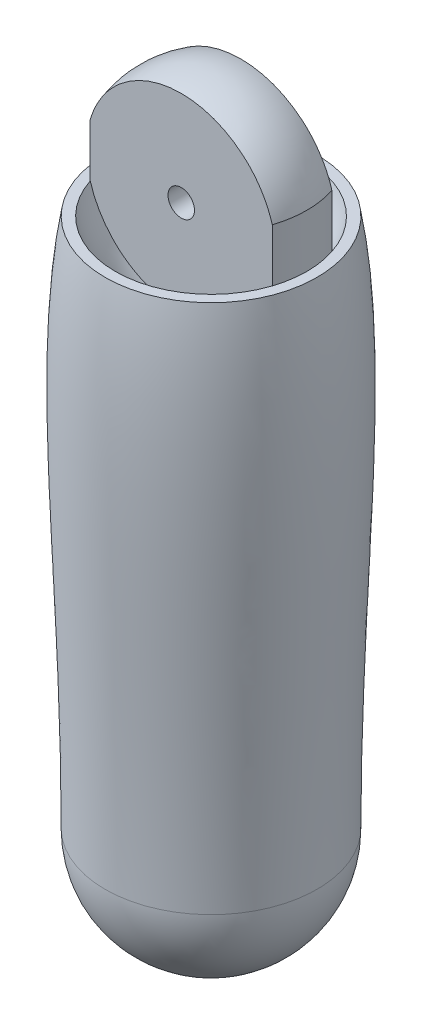
SolidWorks part; units mm, degrees
ref_plane "Front Plane" through (0, 0, 0) normal (0, 0, 1) x (1, 0, 0)
ref_plane "Top Plane" through (0, 0, 0) normal (0, 1, 0) x (1, 0, 0)
ref_plane "Right Plane" through (0, 0, 0) normal (1, 0, 0) x (0, 0, -1)
sketch "Sketch1" plane through (0, 0, 0) normal (1, 0, 0) x (0, 0, -1)
  line L0 (0, 20) -> (0, -20)
  line L1 (0, 20) -> (8, 20)
  line L2 (0, -20) -> (8, -20) construction
  line L3 (13.2094, -9.5442) -> (2.7906, 49.5442) construction
  line L4 (0, -20) -> (0, -28)
  arc A1 (8, -20) -> (0, -28) centre (0, -20) cw
  spline S0 degree 3 poles (8, 20) (9.7365, 10.1519) (8, -3.092) (8, -20) knots 0 0 0 0 1 1 1 1
  point P3 (0, 0)
  dimension "D3" = 100
  dimension "D4" = 30
  dimension "D1" = 40
  dimension "D2" = 8
revolve "Revolve1" add sketch "Sketch1" angle 360 about L0 region at (0, -2.8176, -4.1039)
sketch "Sketch4" plane through (0, 0, 0) normal (1, 0, 0) x (0, 0, -1)
  line L0 (0, 29.5) -> (0, 14.5)
  line L7 (8, 20) -> (-8, 20) construction
  arc A0 (0, 29.5) -> (0, 14.5) centre (0, 22) cw
  dimension "D1" = 15
  dimension "D2" = 2
revolve "Cut-Revolve1" cut sketch "Sketch4" angle 360 about L0
sketch "Sketch5" plane through (0, 0, 0) normal (0, 0, 1) x (1, 0, 0)
  line L1 (0, 14.5) -> (0, 29.5) construction
  line L2 (0, -55) -> (0, 55) construction
  circle A0 centre (0, 22) radius 7.5
extrude "Boss-Extrude1" add sketch "Sketch5" along normal mid plane 4.5
sketch "Sketch6" plane through (0, 20, 0) normal (0, 1, 0) x (1, 0, 0)
  arc A1 (6.8693, 2.25) -> (-6.8693, 2.25) centre (0, 0) ccw construction
  circle A2 centre (0, 0) radius 7.2284
extrude "Cut-Extrude3" cut sketch "Sketch6" along normal through all flip side to cut
ref_plane "Plane1" through (0, 22, 0) normal (0, 1, 0) x (1, 0, 0)
sketch "Sketch7" plane through (0, 22, 0) normal (0, 1, 0) x (1, 0, 0)
  line L0 (-10.1493, 0) -> (11.821, 0) construction
  line L4 (-7.5, 0) -> (-8.9317, 0)
  line L5 (-8.9317, 0) -> (-8.9317, 11.2726)
  line L6 (-8.9317, 11.2726) -> (9.3765, 11.2726)
  line L7 (9.3765, 11.2726) -> (9.3765, 0)
  line L8 (7.5, 0) -> (9.3765, 0)
  arc A3 (7.5, 0) -> (-7.5, 0) centre (0, 0) ccw
  dimension "D1" = 7.5
revolve "Cut-Revolve2" cut sketch "Sketch7" angle 180 about L0
ref_plane "Plane2" through (-8, 0, 0) normal (1, 0, 0) x (0, 0, -1)
sketch "Sketch8" plane through (-8, 0, 0) normal (1, 0, 0) x (0, 0, -1)
  line L0 (8, 20) -> (-8, 20) construction
  circle A0 centre (0, 21) radius 0.75
  dimension "D1" = 1.5
  dimension "D2" = 1
sketch "Sketch10" plane through (0, 0, 0) normal (0, 0, 1) x (1, 0, 0)
  line L1 (-8, 20.25) -> (-8, 21.75) construction
  line L2 (-8, 21) -> (-0.9509, 22.5) construction
  line L3 (-0.9509, 22.5) -> (-0.9509, -10.2742) construction
  spline S0 degree 2 poles (-8, 21) (-0.9509, 22.5) (-0.9509, -10.2742) knots 0 0 0 1 1 1
sweep "Cut-Sweep1" cut profiles "Sketch8" path "Sketch10"
sketch "Sketch12" plane through (0, 0, 0) normal (0, 0, 1) x (1, 0, 0)
  circle A0 centre (0, 22) radius 1
  arc A1 (6.8693, 24) -> (-6.8693, 24) centre (0, 22) ccw construction
  dimension "D1" = 2
extrude "Cut-Extrude5" cut sketch "Sketch12" against normal up to surface and the other way up to surface up to face at (0, 22, -2.25) other way up to face at (0, 22, 2.25)
